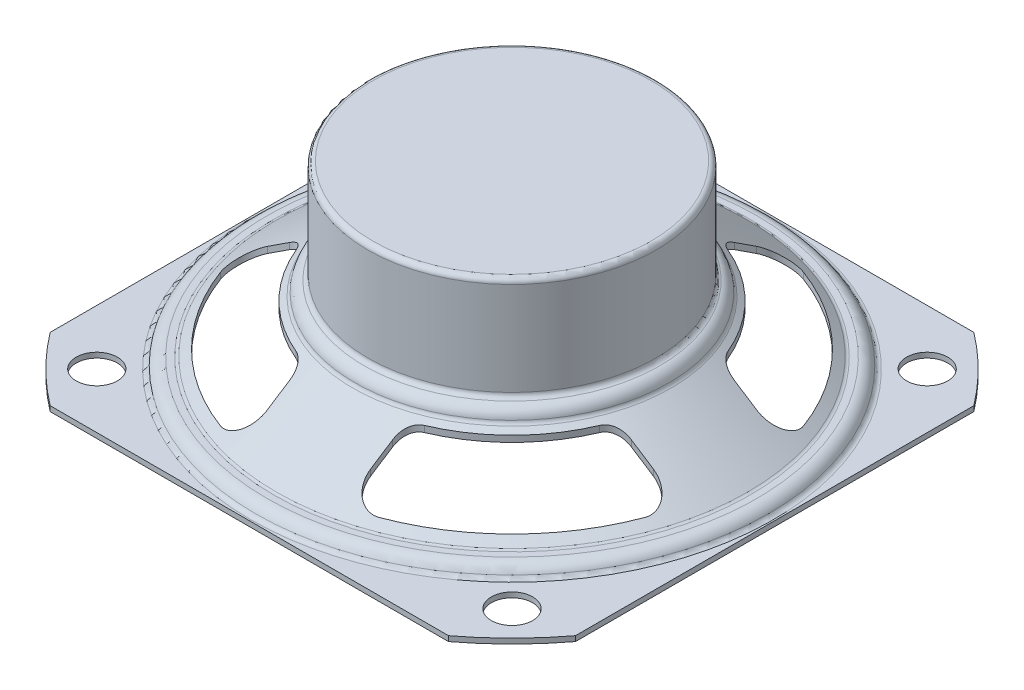
SolidWorks part; units mm, degrees
ref_plane "Front Plane" through (0, 0, 0) normal (0, 0, 1) x (1, 0, 0)
ref_plane "Top Plane" through (0, 0, 0) normal (0, 1, 0) x (1, 0, 0)
ref_plane "Right Plane" through (0, 0, 0) normal (1, 0, 0) x (0, 0, -1)
sketch "Sketch1" plane through (0, 0, 0) normal (0, 0, 1) x (1, 0, 0)
  line L0 (0, -13.4784) -> (0, 15.8799) construction
  line L1 (0, 0) -> (32, 0)
  line L2 (32, 0) -> (32, 0.5)
  line L3 (32, 0.5) -> (25, 0.5)
  line L4 (25, 0.5) -> (25, 1.5)
  line L5 (25, 1.5) -> (23, 1.5)
  line L6 (23, 1.5) -> (15.25, 6.75)
  line L7 (15.25, 6.75) -> (15.25, 8)
  line L8 (15.25, 8) -> (14, 8)
  line L9 (14, 8) -> (14, 18)
  line L10 (14, 18) -> (0, 18)
  line L11 (0, 18) -> (0, 0)
  dimension "D1" = 32
  dimension "D2" = 25
  dimension "D3" = 23
  dimension "D4" = 18
  dimension "D5" = 14
  dimension "D6" = 10
  dimension "D7" = 1.25
  dimension "D8" = 0.5
  dimension "D9" = 1.5
  dimension "D10" = 1.25
revolve "Revolve1" add sketch "Sketch1" angle 360 about L0
shell "Shell1" thickness 0.5 removed face at (0, 0, -32)
fillet "Fillet1" radius 1.25 2 edges at (0, 1.5, -25) (0, 8, -15.25)
sketch "Sketch2" plane through (0, 0.5, 0) normal (0, 1, 0) x (1, 0, 0)
  line L0 (-20, 25.5) -> (-25.5, 20)
  line L1 (20, -25.5) -> (-20, -25.5)
  line L2 (25.5, -20) -> (25.5, 20)
  line L3 (20, 25.5) -> (-20, 25.5)
  line L4 (-25.5, -20) -> (-25.5, 20)
  line L5 (25.5, -25.5) -> (-25.5, 25.5) construction
  line L6 (25.5, 25.5) -> (-25.5, -25.5) construction
  line L7 (-20, -25.5) -> (-25.5, -20)
  line L8 (25.5, -20) -> (20, -25.5)
  line L9 (25.5, 20) -> (20, 25.5)
  circle A0 centre (0, 0) radius 47.7866
  point P0 (0, 0)
  dimension "D1" = 51
extrude "Cut-Extrude1" cut sketch "Sketch2" against normal through all
fillet "Fillet2" radius 0.5 5 edges at (0, 0.5, -25) (0, 6.75, -15.25) (0, 1.5, -23) (0, 8, -14) (0, 18, -14)
sketch "Sketch3" plane through (0, 0.5, 0) normal (0, 1, 0) x (1, 0, 0)
  line L0 (-22.6274, 22.6274) -> (22.6274, -22.6274) construction
  line L1 (0, 0) -> (55.3451, 0) construction
  line L2 (0, 0) -> (0, -38.9275) construction
  line L3 (0, -38.9275) -> (5, -38.9275) construction
  line L4 (5, -38.9275) -> (5, -5) construction
  line L5 (5, -5) -> (55.3451, -5) construction
  line L6 (5, -15.1987) -> (5, -21.4243)
  line L7 (15.1987, -5) -> (21.4243, -5)
  arc A0 (-19.3326, 25.5) -> (-25.5, 19.3326) centre (0, 0) ccw construction
  arc A1 (19.3326, -25.5) -> (25.5, -19.3326) centre (0, 0) ccw construction
  circle A2 centre (20.1525, -20.1525) radius 2
  arc A3 (15.1987, -5) -> (5, -15.1987) centre (0, 0) cw
  arc A4 (21.4243, -5) -> (5, -21.4243) centre (0, 0) cw
  dimension "D1" = 4
  dimension "D4" = 16
  dimension "D5" = 22
  dimension "D2" = 3.5
  dimension "D3" = 5
extrude "Cut-Extrude2" cut sketch "Sketch3" against normal mid plane 40
fillet "Fillet3" radius 2 4 edges at (5, 1.8755, 21.4243) (21.4243, 1.8755, 5) (5, 5.94, 15.1987) (15.1987, 5.94, 5)
pattern_circular "CirPattern1" count 4 over 360 about axis through (0, -13.4784, 0) along (0, -1, 0) of "Cut-Extrude2", "Fillet3"
